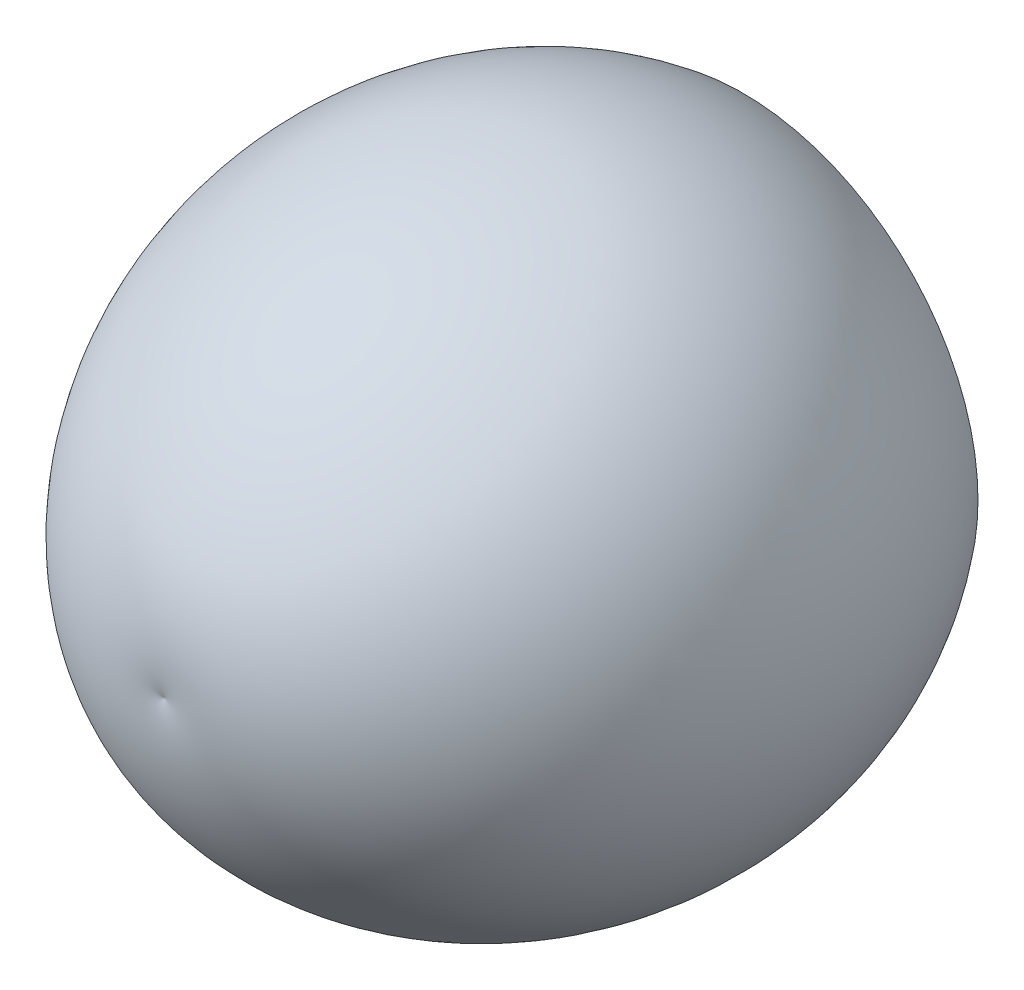
SolidWorks part; units mm, degrees
ref_plane "Front Plane" through (0, 0, 0) normal (0, 0, 1) x (1, 0, 0)
ref_plane "Top Plane" through (0, 0, 0) normal (0, 1, 0) x (1, 0, 0)
ref_plane "Right Plane" through (0, 0, 0) normal (1, 0, 0) x (0, 0, -1)
sketch "Sketch1" plane through (0, 0, 0) normal (0, 1, 0) x (1, 0, 0)
  line L0 (0, -1000) -> (0, 49000) construction
  line L1 (0, -737.2981) -> (0, 49262.7019) construction
  line L2 (106.6962, 262.7019) -> (0, 262.7019)
  line L3 (0, 0) -> (0, 262.7019)
  spline S0 degree 4 poles (0, 0) (0.0438, -0.0187) (0.132, -0.0548) (0.3102, -0.1223) (0.6704, -0.247) (1.1714, -0.401) (1.8156, -0.5742) (2.7509, -0.7924) (3.8882, -1.0127) (5.2292, -1.2184) (6.7739, -1.3928) (8.7253, -1.5446) (11.0843, -1.6282) (13.6441, -1.6002) (16.3987, -1.4464) (19.5282, -1.1549) (23.0244, -0.6824) (27.0731, 0.0616) (32.7937, 1.4224) (39.543, 3.4909) (47.2245, 6.4674) (57.5563, 11.4364) (69.4027, 18.571) (82.2967, 28.3725) (95.6199, 41.2796) (107.5632, 55.8609) (117.828, 71.6659) (126.3413, 88.4773) (133.037, 106.0909) (137.2522, 122.0307) (139.6574, 135.9462) (140.8417, 147.6474) (141.2917, 157.0454) (141.2331, 167.6303) (140.4299, 179.3674) (138.9416, 189.8542) (137.0202, 199.0657) (135.2585, 205.8964) (133.9558, 210.4152) (132.5252, 214.8951) (130.9667, 219.3322) (129.2809, 223.7225) (127.6947, 227.5196) (126.2562, 230.7397) (124.7547, 233.931) (123.4514, 236.5651) (122.0957, 239.1733) (120.4074, 242.2691) (118.6563, 245.3319) (116.8304, 248.3475) (114.9256, 251.3192) (113.2922, 253.7573) (112.1158, 255.4548) (111.1019, 256.8802) (110.2028, 258.1142) (109.4934, 259.0757) (108.6703, 260.1648) (107.9695, 261.0832) (107.045, 262.2639) (106.4669, 262.9922) (105.638, 264.0216) (104.999, 264.8) (104.1024, 265.8801) (103.0609, 267.1073) (101.7997, 268.5594) (100.3516, 270.1759) (98.8702, 271.7824) (97.3707, 273.36) (95.8444, 274.9191) (94.297, 276.4527) (92.7255, 277.9643) (91.1321, 279.4512) (89.5159, 280.9143) (87.878, 282.3524) (86.2181, 283.7655) (84.5369, 285.1529) (83.2601, 286.1741) (82.4021, 286.846) (81.9713, 287.1798) knots 0 0 0 0 0 0.000497 0.000993 0.001987 0.003973 0.00596 0.007947 0.011998 0.016049 0.0201 0.024151 0.032401 0.04065 0.046779 0.052907 0.065164 0.077421 0.089677 0.11419 0.138702 0.163215 0.209093 0.258119 0.307144 0.35617 0.405195 0.454221 0.503246 0.552271 0.576784 0.601297 0.62581 0.650322 0.687091 0.72386 0.736117 0.748373 0.76063 0.772886 0.785142 0.797399 0.809655 0.815783 0.821911 0.834168 0.840296 0.846424 0.85868 0.870937 0.877065 0.883193 0.889321 0.892385 0.895449 0.898861 0.902273 0.905684 0.909096 0.911937 0.914777 0.917618 0.920459 0.92614 0.931822 0.937503 0.943185 0.948866 0.954548 0.960229 0.965911 0.971592 0.977274 0.982955 0.988637 0.994318 1 1 1 1 1 construction
  spline S1 degree 4 poles (0, 0) (0.0438, -0.0187) (0.132, -0.0548) (0.3102, -0.1223) (0.6704, -0.247) (1.1714, -0.401) (1.8156, -0.5742) (2.7509, -0.7924) (3.8882, -1.0127) (5.2292, -1.2184) (6.7739, -1.3928) (8.7253, -1.5446) (11.0843, -1.6282) (13.6441, -1.6002) (16.3987, -1.4464) (19.5282, -1.1549) (23.0244, -0.6824) (27.0731, 0.0616) (32.7937, 1.4224) (39.543, 3.4909) (47.2245, 6.4674) (57.5563, 11.4364) (69.4027, 18.571) (82.2967, 28.3725) (95.6199, 41.2796) (107.5632, 55.8609) (117.828, 71.6659) (126.3413, 88.4773) (133.037, 106.0909) (137.2522, 122.0307) (139.6574, 135.9462) (140.8417, 147.6474) (141.2917, 157.0454) (141.2331, 167.6303) (140.4299, 179.3674) (138.9416, 189.8542) (137.0202, 199.0657) (135.2585, 205.8964) (133.9558, 210.4152) (132.5252, 214.8951) (130.9667, 219.3322) (129.2809, 223.7225) (127.6947, 227.5196) (126.2562, 230.7397) (124.7547, 233.931) (123.4514, 236.5651) (122.0957, 239.1733) (120.4074, 242.2691) (118.6563, 245.3319) (116.8304, 248.3475) (114.9256, 251.3192) (113.2922, 253.7573) (112.1158, 255.4548) (111.1019, 256.8802) (110.2028, 258.1142) (109.4934, 259.0757) (108.6703, 260.1648) (107.9695, 261.0832) (107.2459, 262.0074) (106.8813, 262.4691) (106.6962, 262.7019) knots 0 0 0 0 0 0.000497 0.000993 0.001987 0.003973 0.00596 0.007947 0.011998 0.016049 0.0201 0.024151 0.032401 0.04065 0.046779 0.052907 0.065164 0.077421 0.089677 0.11419 0.138702 0.163215 0.209093 0.258119 0.307144 0.35617 0.405195 0.454221 0.503246 0.552271 0.576784 0.601297 0.62581 0.650322 0.687091 0.72386 0.736117 0.748373 0.76063 0.772886 0.785142 0.797399 0.809655 0.815783 0.821911 0.834168 0.840296 0.846424 0.85868 0.870937 0.877065 0.883193 0.889321 0.892385 0.895449 0.898861 0.902273 0.905684 0.909096 0.909096 0.909096 0.909096 0.909096
revolve "Revolve1" add sketch "Sketch1" angle 360 about L1
